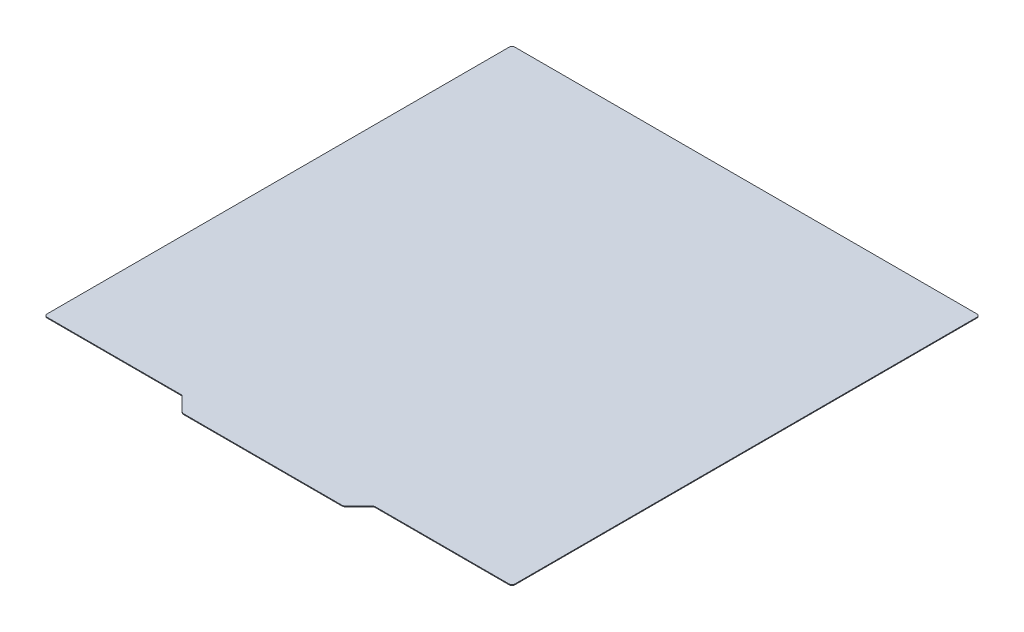
SolidWorks part; units mm, degrees
material "AISI Type 316L stainless steel"
ref_plane "Front Plane" through (0, 0, 0) normal (0, 0, 1) x (1, 0, 0)
ref_plane "Top Plane" through (0, 0, 0) normal (0, 1, 0) x (1, 0, 0)
ref_plane "Right Plane" through (0, 0, 0) normal (1, 0, 0) x (0, 0, -1)
sketch "Sketch1" plane through (0, 0, 0) normal (0, 1, 0) x (1, 0, 0)
  line L0 (-52.5, -162.5) -> (52.5, -162.5)
  line L1 (152.5, -152.5) -> (62.5, -152.5)
  line L2 (152.5, -152.5) -> (152.5, 152.5)
  line L3 (152.5, 152.5) -> (-152.5, 152.5)
  line L4 (-152.5, -152.5) -> (-152.5, 152.5)
  line L5 (152.5, -152.5) -> (-152.5, 152.5) construction
  line L6 (152.5, 152.5) -> (-152.5, -152.5) construction
  line L7 (52.5, -162.5) -> (62.5, -152.5)
  line L8 (-52.5, -162.5) -> (-62.5, -152.5)
  line L9 (-62.5, -152.5) -> (-152.5, -152.5)
  point P0 (0, 0)
  point P8 (0, -162.5)
  point P11 (51.1938, -162.5)
  dimension "D1" = 305
  dimension "D2" = 10
  dimension "D3" = 105
extrude "Boss-Extrude1" add sketch "Sketch1" along normal blind 0.5
fillet "Fillet1" radius 2 8 edges at (-152.5, 0.25, -152.5) (152.5, 0.25, -152.5) (152.5, 0.25, 152.5) (62.5, 0.25, 152.5) (-52.5, 0.25, 162.5) (-62.5, 0.25, 152.5) (-152.5, 0.25, 152.5) (52.5, 0.25, 162.5)
